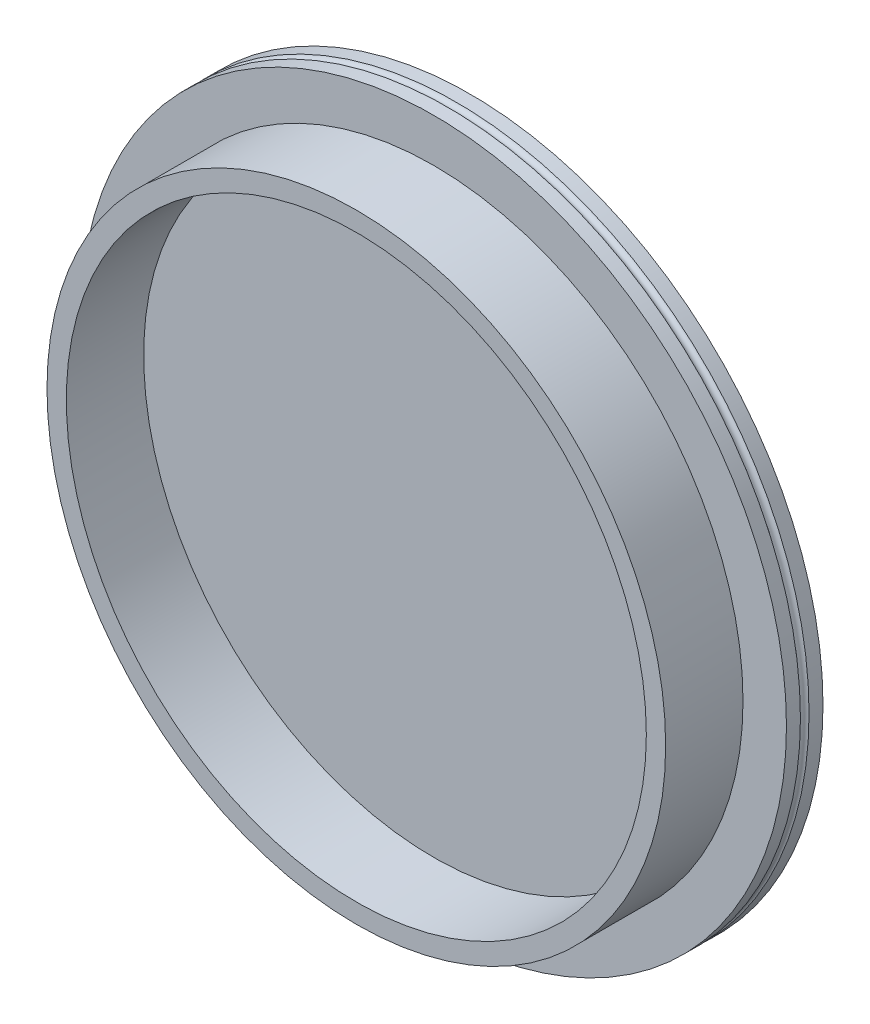
SolidWorks part; units mm, degrees
ref_plane "Front" through (0, 0, 0) normal (0, 0, 1) x (1, 0, 0)
ref_plane "Top" through (0, 0, 0) normal (0, 1, 0) x (1, 0, 0)
ref_plane "Right" through (0, 0, 0) normal (1, 0, 0) x (0, 0, -1)
ref_axis "Axis1" through (0, 0, -80.9) along (0, 0, 1)
sketch "Sketch1" plane through (0, 0, 0) normal (1, 0, 0) x (0, 0, -1)
  line L0 (-12, 0) -> (0, 0) construction
  line L4 (-4.5858, 115.875) -> (0, 115.875)
  line L6 (0, 113.375) -> (-2, 113.375)
  line L7 (-12, 101.6) -> (-12, 115.875)
  line L8 (-2, 113.375) -> (-2, 107.375)
  line L9 (-12, 115.875) -> (-7.4142, 115.875)
  line L10 (-2, 107.375) -> (0, 107.375)
  line L11 (0, 115.875) -> (0, 113.375)
  line L12 (0, 107.375) -> (0, 0)
  line L13 (0, 0) -> (-12, 0)
  line L14 (-12, 101.6) -> (-37.4, 101.6)
  line L15 (-37.4, 101.6) -> (-37.4, 95.25)
  line L16 (-37.4, 95.25) -> (-12, 95.25)
  line L17 (-12, 95.25) -> (-12, 0)
  arc A0 (-7.4142, 115.875) -> (-4.5858, 115.875) centre (-6, 116.375) ccw
  dimension "D6" = 3
  dimension "D9" = 1
  dimension "D2" = 25.4
  dimension "D4" = 231.75
  dimension "D5" = 12
  dimension "D8" = 6.35
  dimension "D10" = 214.75
  dimension "D11" = 6
  dimension "D12" = 2
  dimension "D13" = 95.25
revolve "Base-Revolve" add sketch "Sketch1" angle 360 about L0
sketch "Sketch2" [suppressed] plane through (0, 0, 0) normal (0, 0, -1) x (-1, 0, 0)
  line L1 (79.5782, 49.0982) -> (-79.5782, 49.0982)
  line L2 (85.9282, 42.7482) -> (85.9282, -42.7482)
  line L3 (79.5782, -49.0982) -> (-79.5782, -49.0982)
  line L4 (-85.9282, 42.7482) -> (-85.9282, -42.7482)
  arc A0 (85.9282, 42.7482) -> (79.5782, 49.0982) centre (79.5782, 42.7482) ccw
  arc A1 (79.5782, -49.0982) -> (85.9282, -42.7482) centre (79.5782, -42.7482) ccw
  arc A2 (-85.9282, -42.7482) -> (-79.5782, -49.0982) centre (-79.5782, -42.7482) ccw
  arc A3 (-79.5782, 49.0982) -> (-85.9282, 42.7482) centre (-79.5782, 42.7482) ccw
  dimension "D1" = 6.35
